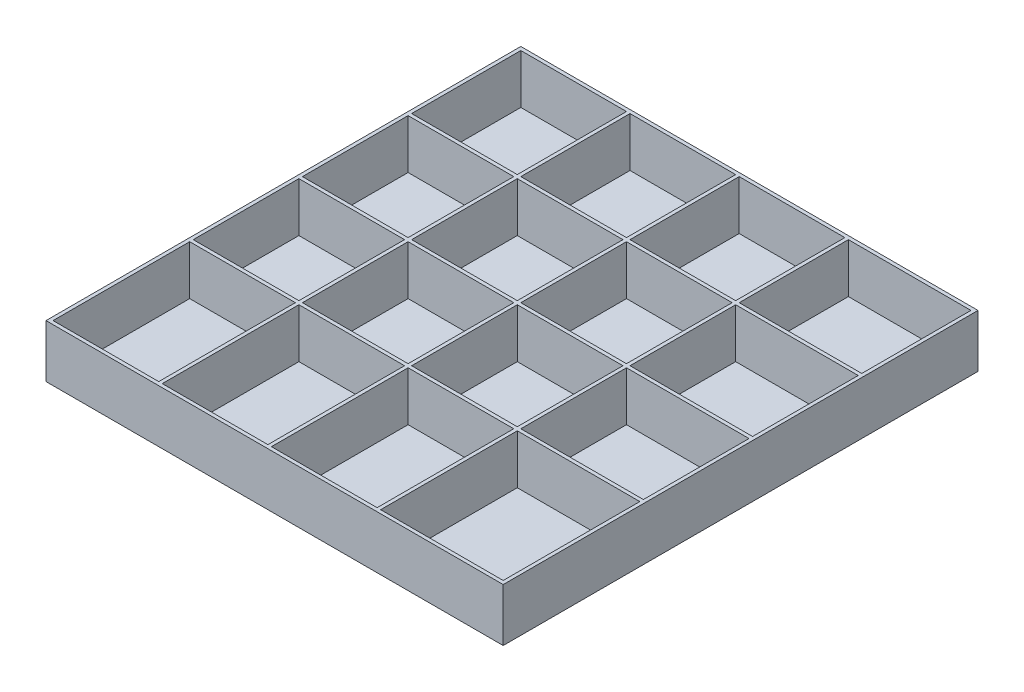
SolidWorks part; units mm, degrees
ref_plane "前视基准面" through (0, 0, 0) normal (0, 0, 1) x (1, 0, 0)
ref_plane "上视基准面" through (0, 0, 0) normal (0, 1, 0) x (1, 0, 0)
ref_plane "右视基准面" through (0, 0, 0) normal (1, 0, 0) x (0, 0, -1)
other "Configuration Table"
sketch "草图1" plane through (0, 0, 0) normal (0, 1, 0) x (1, 0, 0)
  line L1 (129.8, -134.8) -> (-129.8, -134.8)
  line L2 (129.8, -134.8) -> (129.8, 134.8)
  line L3 (129.8, 134.8) -> (-129.8, 134.8)
  line L4 (-129.8, -134.8) -> (-129.8, 134.8)
  line L5 (129.8, -134.8) -> (-129.8, 134.8) construction
  line L6 (129.8, 134.8) -> (-129.8, -134.8) construction
  point P0 (0, 0)
  dimension "D1" = 259.6
  dimension "D2" = 269.6
extrude "凸台-拉伸1" add sketch "草图1" along normal blind 2
sketch "草图2" plane through (0, 2, 0) normal (0, 1, 0) x (1, 0, 0)
  line L0 (127.8, 132.8) -> (-127.8, 132.8)
  line L1 (-127.8, 132.8) -> (-127.8, -132.8)
  line L2 (-127.8, -132.8) -> (127.8, -132.8)
  line L3 (127.8, -132.8) -> (127.8, 132.8)
  line L4 (-129.8, 134.8) -> (-129.8, -134.8)
  line L5 (-129.8, -134.8) -> (129.8, -134.8)
  line L6 (129.8, -134.8) -> (129.8, 134.8)
  line L7 (129.8, 134.8) -> (-129.8, 134.8)
  line L8 (-129.8, 134.8) -> (-129.8, -134.8)
  line L9 (-129.8, -134.8) -> (129.8, -134.8)
  line L10 (129.8, -134.8) -> (129.8, 134.8)
  line L11 (129.8, 134.8) -> (-129.8, 134.8)
  dimension "D1" = 0
  dimension "D2" = 2
extrude "凸台-拉伸2" add sketch "草图2" along normal blind 28
sketch "草图3" plane through (0, 2, 0) normal (0, 1, 0) x (1, 0, 0)
  line L0 (-67.8, 132.8) -> (-67.8, -132.8)
  line L1 (-65.8, 132.8) -> (-65.8, -132.8)
  line L2 (-127.8, 132.8) -> (-127.8, -132.8) construction
  line L4 (127.8, -132.8) -> (127.8, 132.8)
  line L5 (127.8, 132.8) -> (-127.8, 132.8)
  line L6 (-127.8, 132.8) -> (-127.8, -132.8)
  line L7 (-127.8, -132.8) -> (127.8, -132.8)
  line L9 (-65.8, 132.8) -> (-67.8, 132.8)
  line L11 (-67.8, -132.8) -> (-65.8, -132.8)
  dimension "D2" = 60
  dimension "D3" = 2
  dimension "D1" = 0
extrude "凸台-拉伸3" add sketch "草图3" along normal blind 28
pattern_linear "阵列(线性)1" count 3 spacing 62 along (1, 0, 0) of "凸台-拉伸3"
sketch "草图4" plane through (0, 2, 0) normal (0, 1, 0) x (1, 0, 0)
  line L0 (-127.8, 70.8) -> (127.8, 70.8)
  line L1 (-127.8, 68.8) -> (127.8, 68.8)
  line L2 (127.8, 132.8) -> (58.2, 132.8) construction
  line L3 (-127.8, 132.8) -> (-127.8, -132.8) construction
  line L12 (-127.8, 70.8) -> (-127.8, 68.8)
  line L15 (127.8, -132.8) -> (127.8, 132.8)
  line L16 (127.8, 68.8) -> (127.8, 70.8)
  line L17 (127.8, 132.8) -> (58.2, 132.8)
  line L18 (58.2, 132.8) -> (58.2, -132.8)
  line L20 (58.2, -132.8) -> (127.8, -132.8)
  dimension "D2" = 62
  dimension "D3" = 2
  dimension "D1" = 0
extrude "凸台-拉伸5" add sketch "草图4" along normal blind 28
pattern_linear "阵列(线性)2" count 3 spacing 62 along (0, 0, 1) of "凸台-拉伸5"
